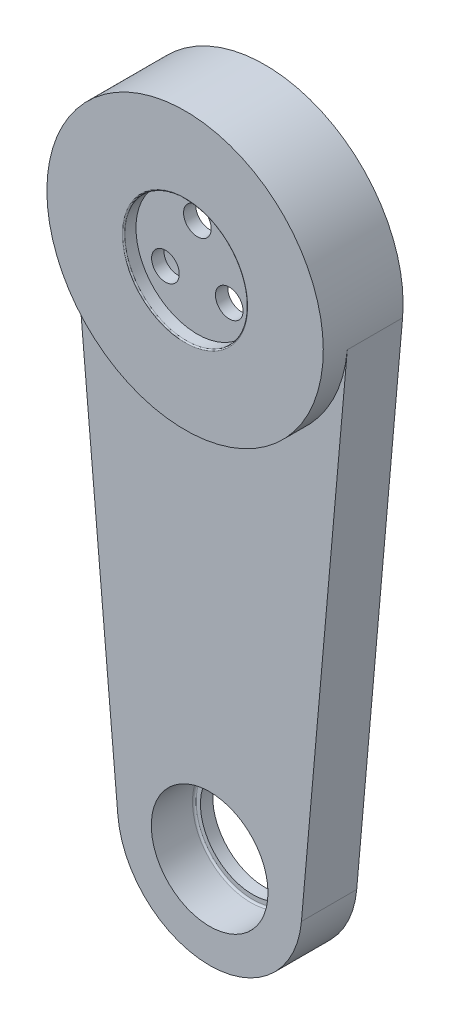
SolidWorks part; units mm, degrees
other "마크업1"
sketch "스케치14" plane through (30, 31, -30.5354) normal (0.2605, 0.9636, -0.0594) x (0.9655, -0.2601, 0.014)
sketch "스케치15" plane through (30, 31, -30.5354) normal (0.2605, 0.9636, -0.0594) x (0.9655, -0.2601, 0.014)
sketch "스케치16" plane through (30, 31, -30.5354) normal (0.2605, 0.9636, -0.0594) x (0.9655, -0.2601, 0.014)
sketch "스케치21" plane through (30, 31, -30.5354) normal (0.2605, 0.9636, -0.0594) x (0.9655, -0.2601, 0.014)
sketch "스케치23" plane through (30, 275, -27) normal (0.2605, 0.9636, -0.0594) x (0.9655, -0.2601, 0.014)
sketch "스케치28" plane through (20, 265, -24) normal (0.2605, 0.9636, -0.0594) x (0.9655, -0.2601, 0.014)
sketch "스케치31" plane through (20, 265, -24) normal (0.2605, 0.9636, -0.0594) x (0.9655, -0.2601, 0.014)
sketch "스케치32" plane through (20, 265, -23) normal (0.2605, 0.9636, -0.0594) x (0.9655, -0.2601, 0.014)
sketch "스케치33" plane through (20, 265, -23) normal (0.2605, 0.9636, -0.0594) x (0.9655, -0.2601, 0.014)
sketch "스케치52" plane through (24, 65, -12) normal (0.2605, 0.9636, -0.0594) x (0.9655, -0.2601, 0.014)
sketch "스케치61" plane through (22.5, 22.5, -13) normal (0.2605, 0.9636, -0.0594) x (0.9655, -0.2601, 0.014)
sketch "스케치64" plane through (22.5, 22.5, -13) normal (0.2605, 0.9636, -0.0594) x (0.9655, -0.2601, 0.014)
material "7075-T6, 플레이트 (SS)"
ref_plane "정면" through (0, 0, 0) normal (0, 0, 1) x (1, 0, 0)
ref_plane "윗면" through (0, 0, 0) normal (0, 1, 0) x (1, 0, 0)
ref_plane "우측면" through (0, 0, 0) normal (1, 0, 0) x (0, 0, -1)
sketch "스케치2" plane through (0, 6, 0) normal (0, 0, -1) x (1, 0, 0)
  circle A0 centre (0, 6) radius 22.5
  dimension "D1" = 45
extrude "보스-돌출2" add sketch "스케치2" along normal blind 2
sketch "스케치22" plane through (0, 0, 0) normal (0, 0, 1) x (1, 0, 0)
  circle A0 centre (0, 0) radius 10
  dimension "D1" = 20
extrude "컷-돌출1" cut sketch "스케치22" against normal blind 2 contours A0
fillet "필렛4" radius 0.2 1 edges at (10, 0, 0)
sketch "스케치54" plane through (0, 0, -2) normal (0, 0, -1) x (-1, 0, 0)
  circle A4 centre (0, 0) radius 22.5 construction
  circle A5 centre (0, 0) radius 22.5
extrude "보스-돌출6" add sketch "스케치54" along normal blind 11
sketch "스케치55" plane through (0, 0, -13) normal (0, 0, -1) x (-1, 0, 0)
  circle A0 centre (0, 0) radius 18.5
  dimension "D1" = 37
extrude "컷-돌출2" cut sketch "스케치55" against normal blind 8
sketch "스케치56" plane through (0, 0, -5) normal (0, 0, -1) x (-1, 0, 0)
  circle A0 centre (0, 0) radius 6 construction
  point P3 (0, 6)
  dimension "D1" = 12
hole_wizard "M4 육각 소켓 머리 캡 나사용 카운터보어1" positions "스케치57" profile "스케치58" counterbore size "M4" standard "ISO" end condition through all
sketch "스케치57" plane through (0, 0, -5) normal (0, 0, -1) x (-1, 0, 0)
  point P0 (0, 6)
sketch "스케치58" plane through (0, 6, -5) normal (1, 0, 0) x (0, 1, 0)
  line L0 (0, 0) -> (0, 5)
  line L1 (0, 5) -> (2.25, 5)
  line L3 (2.25, 5) -> (2.25, 1)
  line L4 (2.25, 1) -> (4, 1)
  line L5 (4, 1) -> (4, 0)
  line L7 (4, 0) -> (0, 0)
  line L11 (0, -6.35) -> (0, 107.95) construction
  dimension "관통 구멍 지름" = 4.5
  dimension "관통 구멍 깊이" = 5
  dimension "카운터보어 지름" = 8
  dimension "카운터보어 깊이" = 1
pattern_circular "원형 패턴1" count 3 over 360 about axis through (0, 0, -2) along (0, 0, 1) of "M4 육각 소켓 머리 캡 나사용 카운터보어1"
sketch "스케치59" plane through (0, 0, -5) normal (0, 0, -1) x (-1, 0, 0)
  circle A0 centre (0, 0) radius 17.5
  circle A1 centre (0, 0) radius 18.5 construction
  circle A2 centre (0, 0) radius 18.5
  dimension "D1" = 35
extrude "보스-돌출7" add sketch "스케치59" along normal blind 1
sketch "스케치60" plane through (0, 0, -13) normal (0, 0, -1) x (-1, 0, 0)
  line L0 (-22.4122, -1.9853) -> (-14.9415, -86.3235)
  line L1 (0, 0) -> (0, -85) construction
  line L2 (22.4122, -1.9853) -> (14.9415, -86.3235)
  circle A0 centre (0, 0) radius 22.5 construction
  arc A1 (-14.9415, -86.3235) -> (14.9415, -86.3235) centre (0, -85) ccw
  arc A2 (-22.4122, -1.9853) -> (22.4122, -1.9853) centre (0, 0) ccw
  point P7 (0, 0)
  dimension "D2" = 30
  dimension "D1" = 85
extrude "보스-돌출8" add sketch "스케치60" against normal blind 9
fillet "필렛6" radius 0.3 1 edges at (-18.5, 0, -6)
sketch "스케치68" plane through (0, 0, -4) normal (0, 0, 1) x (1, 0, 0)
  circle A0 centre (0, -85) radius 9.5
  dimension "D1" = 19
extrude "컷-돌출7" cut sketch "스케치68" against normal blind 7
sketch "스케치69" plane through (0, 0, -11) normal (0, 0, 1) x (1, 0, 0)
  circle A0 centre (0, -85) radius 8.5
  dimension "D1" = 17
extrude "컷-돌출8" cut sketch "스케치69" against normal through all
fillet "필렛7" radius 0.3 1 edges at (9.5, -85, -11)
